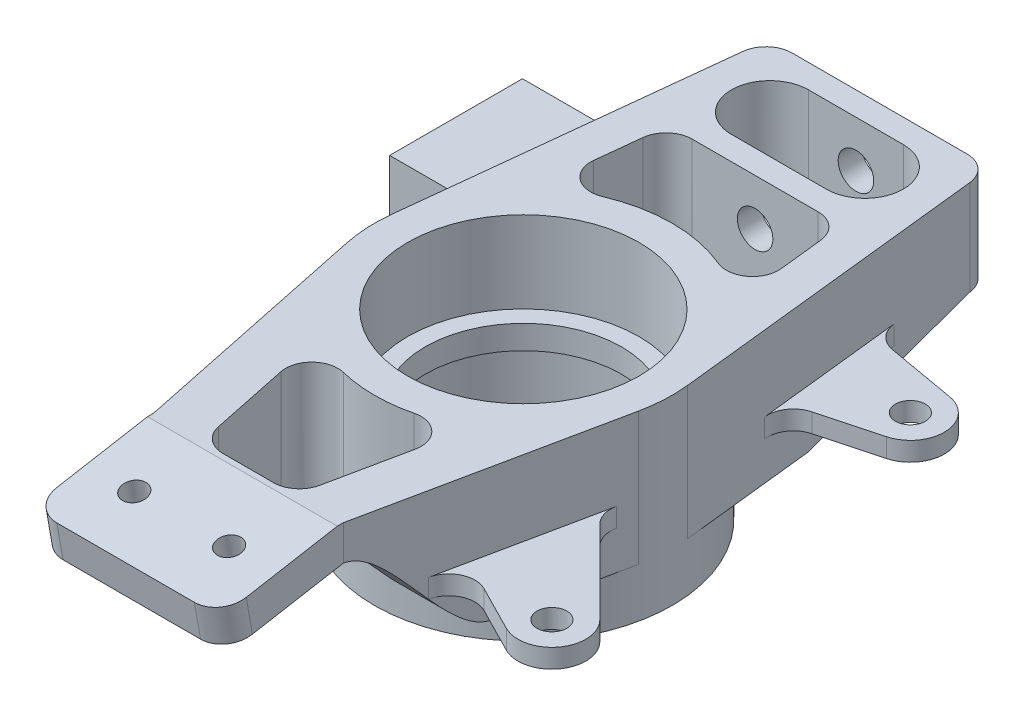
SolidWorks part; units mm, degrees
material "6061-T6 (SS)"
ref_plane "Front Plane" through (0, 0, 0) normal (0, 0, 1) x (1, 0, 0)
ref_plane "Top Plane" through (0, 0, 0) normal (0, 1, 0) x (1, 0, 0)
ref_plane "Right Plane" through (0, 0, 0) normal (1, 0, 0) x (0, 0, -1)
sketch "UBJ LBJ Geometry" plane through (0, 0, 0) normal (1, 0, 0) x (0, 0, -1)
  line L0 (0, 0) -> (0, -97.4059) construction
  line L1 (0, 0) -> (-30.7529, 0) construction
  line L2 (0, 22) -> (-45.5659, 22) construction
  line L3 (0, -10.5425) -> (-23.1063, -10.5425) construction
  line L4 (-84.7344, -51.66) -> (78.74, -22.958) construction
  line L5 (50.8, 0) -> (50.8, -88.2735) construction
  circle A0 centre (-84.7344, -51.66) radius 10.3251 construction
  circle A1 centre (78.74, -22.958) radius 10.3251 construction
  dimension "D7" = 20.6502
  dimension "D8" = 20.6502
  dimension "D1" = 22
  dimension "D2" = 32.5425
  dimension "D3" = 44.958
  dimension "D4" = 73.66
  dimension "D5" = 84.7344
  dimension "D6" = 78.74
  dimension "D9" = 50.8
ref_plane "Wheel Face " through (0, 22, 0) normal (0, -1, 0) x (-1, 0, 0)
ref_plane "Upright Face" through (0, -10.5425, 0) normal (0, -1, 0) x (-1, 0, 0)
ref_plane "Tie Bracket Plane" through (0, 0, -50.8) normal (0, 0, 1) x (1, 0, 0)
sketch "Tie Bracket Geometry" plane through (0, 0, -50.8) normal (0, 0, 1) x (1, 0, 0)
  line L0 (0, -27.8636) -> (-60.5599, -51.4749) construction
  line L4 (0, 200000) -> (0, -200097.4059) construction
  circle A0 centre (-60.5599, -51.4749) radius 8.948 construction
  dimension "D1" = 65
  dimension "D2" = 68.7
sketch "Sketch1" plane through (0, 0, 0) normal (0, 0, 1) x (1, 0, 0)
  line L1 (-75.0953, -10.5425) -> (75.0953, -10.5425) construction
  line L2 (-39.878, -10.5425) -> (-39.878, -59.3105)
  line L3 (-39.878, -59.3105) -> (-32.258, -59.3105)
  line L4 (-32.258, -59.3105) -> (-32.258, -63.1205)
  line L5 (-32.258, -63.1205) -> (-31.0007, -63.1205)
  line L8 (-31.0007, -10.5425) -> (-31.0007, -32.3865)
  line L9 (-31.0007, -32.3865) -> (-26.289, -32.3865)
  line L10 (-26.289, -32.3865) -> (-26.289, -38.7365)
  line L11 (-26.289, -38.7365) -> (-31.0007, -38.7365)
  line L12 (-31.0007, -38.7365) -> (-31.0007, -63.1205)
  line L15 (-39.878, -10.5425) -> (-31.0007, -10.5425)
  line L17 (0, 0) -> (0, -23.5057) construction
  dimension "D1" = 6.35
  dimension "D2" = 62.0014
  dimension "D3" = 24.384
  dimension "D4" = 52.578
  dimension "D5" = 21.844
  dimension "D6" = 48.768
  dimension "D7" = 79.756
  dimension "D8" = 64.516
revolve "Bearing Housing Revolve" add sketch "Sketch1" angle 360 about L17
fillet "Bearing Housing Fillet" radius 6.35 1 edges at (0, -59.3105, 32.258)
sketch "Sketch2" plane through (0, -10.5425, 0) normal (0, -1, 0) x (-1, 0, 0)
  line L3 (39.878, -40.64) -> (39.878, 0)
  line L4 (-39.878, -40.64) -> (-39.878, 0)
  line L5 (39.878, -40.64) -> (-39.878, -40.64)
  circle A4 centre (0, 0) radius 39.878 construction
  arc A5 (39.878, 0) -> (-39.878, 0) centre (0, 0) cw
  dimension "D1" = 40.64
extrude "UBJ Prep" add sketch "Sketch2" along normal blind 35.56
sketch "Sketch3" plane through (-39.878, 0, 0) normal (-1, 0, 0) x (0, 0, 1)
  line L0 (-120.7672, 22) -> (120.7672, 22) construction
  line L1 (40.64, -10.5425) -> (75.2198, -10.5425)
  line L2 (75.2198, -10.5425) -> (106.4875, -16.0558)
  line L3 (106.4875, -16.0558) -> (104.8335, -25.4361)
  line L4 (104.8335, -25.4361) -> (73.5658, -19.9228)
  line L6 (40.64, -46.1025) -> (40.64, -10.5425)
  line L7 (75.2198, -10.5425) -> (73.5658, -19.9228) construction
  line L8 (89.8445, -22.6794) -> (84.7344, -51.66) construction
  line L10 (40.64, -46.1025) -> (50.8, -46.1025) construction
  line L11 (50.8, -46.1025) -> (63.5, -19.9228) construction
  line L12 (63.5, -19.9228) -> (73.5658, -19.9228) construction
  circle A0 centre (84.7344, -51.66) radius 13.6189 construction
  spline S0 degree 3 poles (40.64, -46.1025) (50.8, -46.1025) (63.5, -19.9228) (73.5658, -19.9228) knots 0 0 0 0 1 1 1 1
  dimension "D1" = 73.66
  dimension "D2" = 84.7344
  dimension "D3" = 9.525
  dimension "D4" = 31.75
  dimension "D5" = 10
  dimension "D6" = 15.24
  dimension "D8" = 50.8
  dimension "D9" = 63.5
extrude "UBJ Extrude " add sketch "Sketch3" against normal up to surface (79.756 mm away) up to face at (39.878, -28.3225, 20.32)
sketch "Sketch4" plane through (0, -6.7415, -1.1887) normal (0, -0.9848, -0.1736) x (1, 0, 0)
  line L0 (0, 107.6578) -> (0, 27.8969) construction
  line L1 (39.878, 107.6578) -> (-39.878, 107.6578) construction
  line L3 (-12.7, 92.4178) -> (12.7, 92.4178) construction
  circle A0 centre (-12.7, 92.4178) radius 3.175
  circle A1 centre (12.7, 92.4178) radius 3.175
  point P8 (0, 92.4178)
  dimension "D2" = 6.35
  dimension "D1" = 25.4
  dimension "D3" = 15.24
extrude "Camber Block Holes" cut sketch "Sketch4" against normal up to surface (9.525 mm away) up to face at (0, -13.2991, 90.8537)
sketch "Sketch5" plane through (0, -46.1025, 0) normal (0, -1, 0) x (1, 0, 0)
  line L0 (-25.4, 104.8335) -> (-25.4, 73.5915)
  line L1 (25.4, 106.4875) -> (39.878, 106.4875)
  line L2 (39.878, 104.8335) -> (-39.878, 104.8335) construction
  line L4 (-25.4, 73.5915) -> (-39.0395, 8.1348)
  line L5 (25.4, 104.8335) -> (25.4, 73.5915)
  line L6 (25.4, 73.5915) -> (39.0395, 8.1348)
  line L7 (-25.4, 104.8335) -> (-25.4, 106.4875)
  line L8 (39.878, 106.4875) -> (-39.878, 106.4875) construction
  line L9 (25.4, 104.8335) -> (25.4, 106.4875)
  line L10 (-25.4, 106.4875) -> (-39.878, 106.4875)
  line L11 (-39.878, 106.4875) -> (-39.878, 0)
  line L12 (39.878, 106.4875) -> (39.878, 0)
  line L13 (-12.4129, 73.66) -> (12.4129, 73.66)
  line L14 (-12.4129, 73.66) -> (-20.6535, 34.1128)
  line L15 (12.4129, 73.66) -> (20.6535, 34.1128)
  arc A0 (-39.878, 0) -> (-39.0395, 8.1348) centre (0, 0) cw
  circle A1 centre (0, 0) radius 39.878 construction
  arc A2 (39.878, 0) -> (-39.878, 0) centre (0, 0) ccw construction
  arc A3 (39.878, 0) -> (39.0395, 8.1348) centre (0, 0) ccw
  arc A4 (-20.6535, 34.1128) -> (20.6535, 34.1128) centre (0, 0) cw
  point P31 (0, 73.66)
  dimension "D1" = 25.4
  dimension "D2" = 12.7
  dimension "D3" = 31.242
  dimension "D4" = 73.66
extrude "Weight Saving" cut sketch "Sketch5" against normal through all
fillet "Fillet2" radius 6.985 4 edges at (20.6535, -28.3225, 34.1128) (-20.6535, -28.3225, 34.1128) (12.4129, -15.2409, 73.66) (-12.4129, -15.2409, 73.66)
sketch "Sketch6" plane through (0, -10.5425, 0) normal (0, -1, 0) x (-1, 0, 0)
  line L0 (-39.878, 0) -> (-39.878, 40.64)
  line L1 (-39.878, 40.64) -> (39.878, 40.64)
  line L2 (39.878, 40.64) -> (39.878, 0)
  circle A0 centre (0, 0) radius 39.878 construction
  arc A1 (-39.878, 0) -> (39.878, 0) centre (0, 0) cw
  dimension "D1" = 40.64
extrude "LBJ Prep" add sketch "Sketch6" along normal blind 35.56
sketch "Sketch8" plane through (-39.878, 0, 0) normal (-1, 0, 0) x (0, 0, 1)
  line L0 (-40.64, -10.5425) -> (-95.4151, -10.5425)
  line L1 (-95.4151, -10.5425) -> (-95.4151, -35.9425)
  line L2 (-95.4151, -35.9425) -> (-89.0651, -35.9425)
  line L7 (-40.64, -46.1025) -> (-40.64, -10.5425)
  line L8 (-120.7672, 22) -> (120.7672, 22) construction
  line L9 (-89.0651, -35.9425) -> (-89.0651, -10.5425) construction
  line L10 (-89.0651, -35.9425) -> (-40.64, -46.1025)
  circle A0 centre (-78.74, -22.958) radius 10.3251 construction
  dimension "D3" = 20.6502
  dimension "D1" = 78.74
  dimension "D2" = 44.958
  dimension "D4" = 6.35
  dimension "D5" = 25.4
extrude "LBJ Area " add sketch "Sketch8" against normal up to surface (79.756 mm away) up to face at (39.878, -28.3225, -20.32)
sketch "Sketch7" plane through (0, -46.1025, 0) normal (0, -1, 0) x (1, 0, 0)
  line L0 (-12.7, -78.74) -> (12.7, -78.74) construction
  line L1 (0, -200000) -> (0, 200045.5659) construction
  line L2 (-12.7, -68.4149) -> (12.7, -68.4149)
  line L3 (-12.7, -89.0651) -> (12.7, -89.0651)
  line L4 (-29.718, -95.4151) -> (-39.6434, -4.3194)
  line L5 (39.878, -95.4151) -> (-39.878, -95.4151) construction
  line L6 (29.718, -95.4151) -> (39.6434, -4.3194)
  line L7 (-29.718, -95.4151) -> (-39.878, -95.4151)
  line L8 (-39.878, -95.4151) -> (-39.878, 0)
  line L9 (29.718, -95.4151) -> (39.878, -95.4151)
  line L10 (39.878, -95.4151) -> (39.878, 0)
  line L13 (-23.1316, -62.0649) -> (23.1316, -62.0649)
  line L14 (23.1316, -62.0649) -> (26.6629, -29.6537)
  line L15 (-23.1316, -62.0649) -> (-26.6629, -29.6537)
  arc A0 (-12.7, -68.4149) -> (-12.7, -89.0651) centre (-12.7, -78.74) ccw
  arc A1 (12.7, -89.0651) -> (12.7, -68.4149) centre (12.7, -78.74) ccw
  circle A2 centre (0, 0) radius 39.878 construction
  arc A3 (-39.878, 0) -> (39.878, 0) centre (0, 0) ccw construction
  arc A4 (39.878, 0) -> (39.6434, -4.3194) centre (0, 0) cw
  arc A5 (-39.878, 0) -> (-39.6434, -4.3194) centre (0, 0) ccw
  arc A6 (-26.6629, -29.6537) -> (26.6629, -29.6537) centre (0, 0) ccw
  point P4 (0, -78.74)
  point P28 (0, -62.0649)
  dimension "D1" = 78.74
  dimension "D2" = 20.6502
  dimension "D3" = 25.4
  dimension "D4" = 10.16
  dimension "D5" = 6.35
  dimension "D6" = 10.16
extrude "LBJ Taper And Slot" cut sketch "Sketch7" against normal up to surface (35.56 mm away)
fillet "Fillet3" radius 6.985 4 edges at (23.1316, -26.0749, -62.0649) (-23.1316, -26.0749, -62.0649) (26.6629, -28.3225, -29.6537) (-26.6629, -28.3225, -29.6537)
extrude "LBJ Holes" cut sketch "Sketch9" against normal up to surface (33.3502 mm away) up to face at (0, -26.0749, -62.0649)
sketch "Sketch9" plane through (0, 0, -95.4151) normal (0, 0, -1) x (-1, 0, 0)
  circle A0 centre (0, -22.958) radius 4.7625
  dimension "D2" = 9.525
  dimension "D1" = 22.958
ref_plane "Brake Mounting Plane" through (0, -30.7025, 0) normal (0, 1, 0) x (1, 0, 0)
sketch "Sketch10" plane through (0, -30.7025, 0) normal (0, 1, 0) x (1, 0, 0)
  line L0 (87.9814, 0) -> (161.3053, 0) construction
  line L1 (0, 72.9505) -> (0, 47.1638) construction
  line L2 (55.6514, 48) -> (55.6514, -48) construction
  line L3 (58.0015, 39.2294) -> (36.4684, 33.4596)
  line L4 (39.6434, 4.3194) -> (29.718, 95.4151) construction
  line L5 (36.4684, 33.4596) -> (33.4531, 61.1342)
  line L6 (33.4531, 61.1342) -> (57.2281, 56.9421)
  line L7 (62.0719, -41.5795) -> (37.244, -16.7515)
  line L8 (25.4, -73.5915) -> (39.0395, -8.1348) construction
  line L9 (37.244, -16.7515) -> (31.2047, -45.7345)
  line L10 (31.2047, -45.7345) -> (51.5292, -56.0903)
  circle A0 centre (55.6514, 48) radius 4
  circle A1 centre (55.6514, -48) radius 4
  arc A2 (51.5292, -56.0903) -> (62.0719, -41.5795) centre (55.6514, -48) ccw
  arc A3 (58.0015, 39.2294) -> (57.2281, 56.9421) centre (55.6514, 48) ccw
  point P7 (55.6514, 0)
  dimension "D2" = 8
  dimension "D3" = 5.08
  dimension "D4" = 5.08
  dimension "D1" = 96
  dimension "D5" = 55.6514
  dimension "D6" = 80
  dimension "D7" = 75
  dimension "D8" = 45
  dimension "D9" = 63
extrude "Brake Mounts" add sketch "Sketch10" against normal blind 5.08
fillet "Fillet4" radius 6.985 4 edges at (37.244, -33.2425, 16.7515) (31.2047, -33.2425, 45.7345) (36.4684, -33.2425, -33.4596) (33.4531, -33.2425, -61.1342)
sketch "Sketch12" plane through (0, 0, -50.8) normal (0, 0, 1) x (1, 0, 0)
  line L0 (0, 3.2946) -> (0, -38.5659) construction
  line L1 (-90.5661, 0) -> (-38.2005, 0) construction
  line L2 (-68.8149, -10.5425) -> (-68.8149, -51.4749)
  line L3 (-52.3049, -10.5425) -> (-52.3049, -51.4749)
  line L4 (-68.8149, -10.5425) -> (-52.3049, -10.5425)
  line L6 (-75.0953, -10.5425) -> (75.0953, -10.5425) construction
  circle A0 centre (-60.5599, -51.4749) radius 3.175
  arc A1 (-68.8149, -51.4749) -> (-52.3049, -51.4749) centre (-60.5599, -51.4749) ccw
  dimension "D1" = 6.35
  dimension "D2" = 5.08
extrude "Initial Toe Bracket" add sketch "Sketch12" along normal blind 17.78 and the other way blind 17.78 separate body
sketch "Sketch13" plane through (-52.3049, 0, 0) normal (1, 0, 0) x (0, 0, -1)
  line L0 (33.02, -25.7825) -> (68.58, -25.7825)
  line L1 (68.58, -51.4749) -> (68.58, -10.5425) construction
  line L2 (68.58, -25.7825) -> (68.58, -38.4825)
  line L3 (33.02, -25.7825) -> (33.02, -38.4825)
  line L5 (33.02, -38.4825) -> (68.58, -38.4825)
  line L6 (33.02, -51.4749) -> (33.02, -10.5425) construction
  line L8 (-75.0953, -10.5425) -> (75.0953, -10.5425) construction
  dimension "D1" = 12.7
  dimension "D2" = 15.24
extrude "Toe Bracket Connection to Upright" add sketch "Sketch13" along normal up to surface (19.6631 mm away) up to face at (-34.1364, -30.8625, -54.8623)
sketch "Sketch14" plane through (0, 0, -68.58) normal (0, 0, -1) x (-1, 0, 0)
  line L0 (52.3049, -25.7825) -> (68.8149, -25.7825)
  line L1 (68.8149, -10.5425) -> (68.8149, -51.4749) construction
  line L2 (68.8149, -25.7825) -> (68.8149, -10.5425)
  line L3 (68.8149, -10.5425) -> (52.3049, -10.5425)
  line L4 (52.3049, -10.5425) -> (52.3049, -25.7825)
extrude "Excess Toe Bracket Cut" cut sketch "Sketch14" against normal up to surface (35.56 mm away) up to face at (-52.4853, -32.6025, -33.02)
sketch "Sketch15" plane through (-68.8149, 0, 0) normal (-1, 0, 0) x (0, 0, 1)
  line L0 (-61.976, -41.9499) -> (-39.624, -41.9499)
  line L1 (-39.624, -41.9499) -> (-39.624, -59.7299)
  line L2 (-68.58, -59.7299) -> (-33.02, -59.7299) construction
  line L3 (-39.624, -59.7299) -> (-61.976, -59.7299)
  line L4 (-61.976, -59.7299) -> (-61.976, -41.9499)
  line L6 (-50.8, -25.7825) -> (-50.8, -39.109) construction
  line L8 (-33.02, -25.7825) -> (-68.58, -25.7825) construction
  point P9 (-50.8, -25.7825)
  point P11 (-50.8, -41.9499)
  dimension "D1" = 22.352
  dimension "D2" = 17.78
extrude "Toe Bracket Slot" cut sketch "Sketch15" against normal up to surface (16.51 mm away) up to face at (-52.3049, -44.9787, -50.8)
fillet "Toe Bracket Fillet" radius 6.985 2 edges at (-32.6418, -32.1325, -68.58) (-36.5163, -32.1325, -33.02)
fillet "Fillet5" radius 6.985 4 edges at (-25.4, -20.746, 105.6605) (25.4, -20.746, 105.6605) (29.718, -23.2425, -95.4151) (-29.718, -23.2425, -95.4151)
equation "\"Wheel_Offset\"= 22mm"
equation "\"HUB_to_UBJ_Lat\"= 2.9in"
equation "\"Hub_to_UBJ_Vert\"= 3.336in"
equation "\"Hub_to_LBJ_Lat\"= 1.77in"
equation "\"Hub_to_LBJ_Vert\"= 3.1in"
equation "\"Wheel_face_to_Upright_back\"= 1.2812in'This is the distance between the whee face to the upright back."
equation "\"UBJ_Angle\"= 12deg"
equation "\"D2@UBJ LBJ Geometry\" = \"Wheel_face_to_Upright_back\""
equation "\"D3@UBJ LBJ Geometry\" = \"Hub_to_LBJ_Lat\""
equation "\"D4@UBJ LBJ Geometry\" = \"HUB_to_UBJ_Lat\""
equation "\"D5@UBJ LBJ Geometry\" = \"Hub_to_UBJ_Vert\""
equation "\"D6@UBJ LBJ Geometry\" = \"Hub_to_LBJ_Vert\""
equation "\"D1@Sketch3\"=\"HUB_to_UBJ_Lat\""
equation "\"D2@Sketch3\"=\"Hub_to_UBJ_Vert\""
equation "\"D1@Sketch8\"=\"Hub_to_LBJ_Vert\""
equation "\"D2@Sketch8\"=\"Hub_to_LBJ_Lat\""
equation "\"Hub_Tie_Bracket_Vert\"= 2in'(Not Given) Ask Sus and Controls later"
equation "\"Tie_Beta\"= 21.3deg'From FE11 Master "
equation "\"Toe_Arm\"= 65mm'From FE11 Master (Assume Dist start at KPI)"
equation "\"D9@UBJ LBJ Geometry\" = \"Hub_Tie_Bracket_Vert\""
equation "\"D1@Sketch7\"=\"Hub_to_LBJ_Vert\""
equation "\"D1@Sketch9\"=\"Hub_to_LBJ_Lat\"-\"Wheel_Offset\""
equation "\"D1@Tie Bracket Geometry\" = \"Toe_Arm\""
equation "\"D2@Tie Bracket Geometry\" = 90 - \"Tie_Beta\""
equation "\"D1@Sketch7\"=\"Hub_to_LBJ_Lat\""
